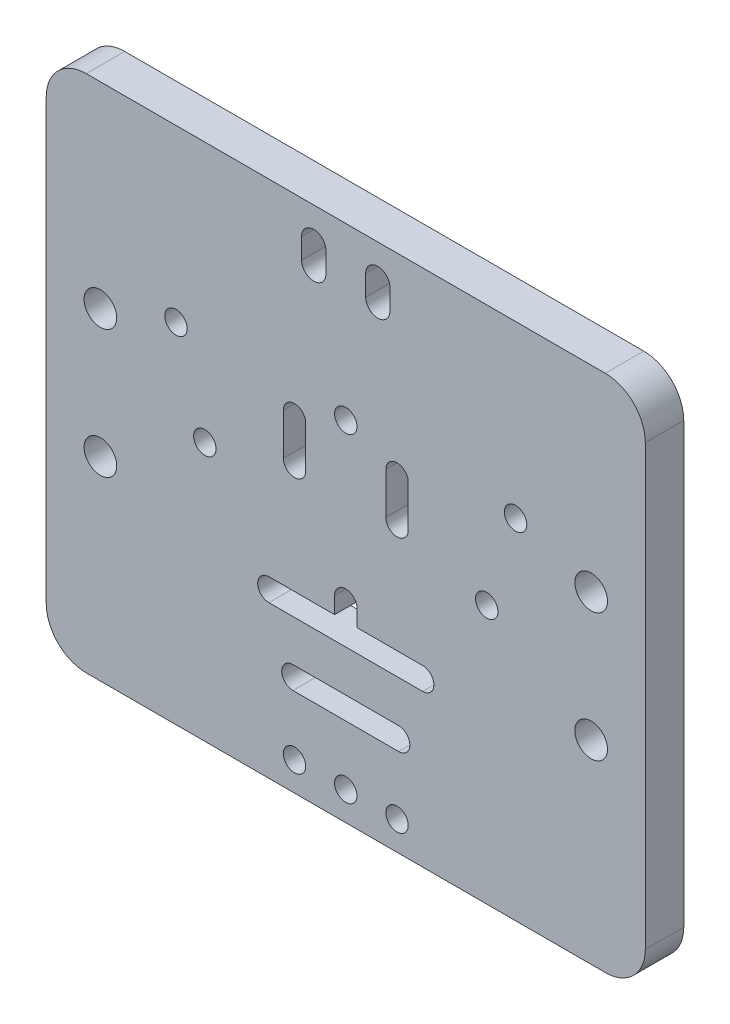
SolidWorks part; units mm, degrees
material "Acrylic (Medium-high impact)"
ref_plane "Спереди" through (0, 0, 0) normal (0, 0, 1) x (1, 0, 0)
ref_plane "Сверху" through (0, 0, 0) normal (0, 1, 0) x (1, 0, 0)
ref_plane "Справа" through (0, 0, 0) normal (1, 0, 0) x (0, 0, -1)
sketch "Model" plane through (0, 0, 0) normal (0, 0, 1) x (1, 0, 0)
  line L0 (0, 0) -> (0, 91.7343) construction
  line L1 (5, 79.6063) -> (5, 68.5159) construction
  line L2 (-2.3648, 54.4) -> (2.3481, 54.4) construction
  line L3 (8, 54.1038) -> (8, 41.41) construction
  line L4 (38.3, 55.3072) -> (38.3, 25.5369) construction
  line L6 (5.2056, 25.5) -> (38.932, 25.5) construction
  line L9 (8, 7.117) -> (8, 1.8707) construction
  line L13 (34.6862, 30.35) -> (41.936, 30.35) construction
  line L14 (34.5552, 50.35) -> (42.4898, 50.35) construction
  line L15 (26.5, 56.989) -> (26.5, 51.9054) construction
  line L16 (23.9154, 54.4) -> (29.241, 54.4) construction
  line L17 (22, 42.5983) -> (22, 38.5529) construction
  line L18 (19.8952, 40.4) -> (24.0146, 40.4) construction
  line L19 (-5, 79.6063) -> (-5, 68.5159) construction
  line L20 (-3.1, 75.8) -> (-3.1, 72.6)
  line L21 (-6.9, 72.6) -> (-6.9, 75.8)
  line L22 (-6.9, 75.8) -> (-6.9, 72.6)
  line L23 (-3.1, 72.6) -> (-3.1, 75.8)
  line L24 (-34.5552, 50.35) -> (-42.4898, 50.35) construction
  line L25 (-34.6862, 30.35) -> (-41.936, 30.35) construction
  line L26 (-38.3, 55.3072) -> (-38.3, 25.5369) construction
  line L27 (-8, 7.117) -> (-8, 1.8707) construction
  line L33 (-19.8952, 40.4) -> (-24.0146, 40.4) construction
  line L34 (-22, 42.5983) -> (-22, 38.5529) construction
  line L35 (-23.9154, 54.4) -> (-29.241, 54.4) construction
  line L36 (-26.5, 56.989) -> (-26.5, 51.9054) construction
  line L37 (-8, 54.1038) -> (-8, 41.41) construction
  line L38 (-9.75, 50.9) -> (-9.75, 44.4)
  line L39 (-6.25, 44.4) -> (-6.25, 50.9)
  line L40 (-6.25, 50.9) -> (-6.25, 44.4)
  line L41 (-9.75, 44.4) -> (-9.75, 50.9)
  line L42 (-8.25, 15.5) -> (8.25, 15.5) construction
  line L1661 (3.1, 72.6) -> (3.1, 75.8)
  line L1674 (6.9, 75.8) -> (6.9, 72.6)
  line L1730 (46.75, 74.75) -> (46.75, 6.25)
  line L1743 (40.5, 0) -> (-40.5, 0)
  line L1756 (-46.75, 6.25) -> (-46.75, 74.75)
  line L1769 (-40.5, 81) -> (40.5, 81)
  line L1807 (8.25, 17.25) -> (-8.25, 17.25)
  line L1820 (-8.25, 13.75) -> (8.25, 13.75)
  line L2052 (6.9, 72.6) -> (6.9, 75.8)
  line L2065 (3.1, 75.8) -> (3.1, 72.6)
  line L2109 (9.75, 44.4) -> (9.75, 50.9)
  line L2122 (6.25, 50.9) -> (6.25, 44.4)
  line L2254 (-1.75, 29.85) -> (-1.75, 27.25)
  line L2255 (-1.75, 27.25) -> (-12, 27.25)
  line L2268 (-12, 23.75) -> (12, 23.75)
  line L2281 (12, 27.25) -> (1.75, 27.25)
  line L2282 (1.75, 27.25) -> (1.75, 29.85)
  line L2413 (6.25, 44.4) -> (6.25, 50.9)
  line L2426 (9.75, 50.9) -> (9.75, 44.4)
  line L2519 (8.25, 13.75) -> (-8.25, 13.75)
  line L2532 (-8.25, 17.25) -> (8.25, 17.25)
  line L2808 (1.75, 29.85) -> (1.75, 27.25)
  line L2809 (1.75, 27.25) -> (12, 27.25)
  line L2822 (12, 23.75) -> (-12, 23.75)
  line L2835 (-12, 27.25) -> (-1.75, 27.25)
  line L2836 (-1.75, 27.25) -> (-1.75, 29.85)
  arc A0 (-46.75, 74.75) -> (-40.5, 81) centre (-40.5, 74.75) cw
  arc A1 (40.5, 81) -> (46.75, 74.75) centre (40.5, 74.75) cw
  arc A2 (46.75, 6.25) -> (40.5, 0) centre (40.5, 6.25) cw
  arc A3 (-46.75, 6.25) -> (-40.5, 0) centre (-40.5, 6.25) ccw
  arc A4 (6.9, 75.8) -> (3.1, 75.8) centre (5, 75.8) ccw
  arc A5 (3.1, 72.6) -> (6.9, 72.6) centre (5, 72.6) ccw
  circle A7 centre (0, 4.5) radius 1.75
  circle A8 centre (8, 4.5) radius 1.75
  arc A11 (-8.25, 17.25) -> (-8.25, 13.75) centre (-8.25, 15.5) ccw
  arc A12 (8.25, 13.75) -> (8.25, 17.25) centre (8.25, 15.5) ccw
  arc A13 (1.75, 29.85) -> (-1.75, 29.85) centre (0, 29.85) ccw
  arc A14 (12, 23.75) -> (12, 27.25) centre (12, 25.5) ccw
  arc A15 (-12, 23.75) -> (-12, 27.25) centre (-12, 25.5) cw
  circle A16 centre (38.3, 50.35) radius 2.55
  circle A17 centre (38.3, 30.35) radius 2.55
  arc A18 (-3.1, 72.6) -> (-6.9, 72.6) centre (-5, 72.6) cw
  arc A19 (-6.9, 75.8) -> (-3.1, 75.8) centre (-5, 75.8) cw
  circle A20 centre (-38.3, 30.35) radius 2.55
  circle A21 centre (-38.3, 50.35) radius 2.55
  circle A22 centre (-8, 4.5) radius 1.75
  circle A26 centre (0, 54.4) radius 1.75
  circle A27 centre (26.5, 54.4) radius 1.75
  circle A28 centre (22, 40.4) radius 1.75
  arc A29 (9.75, 50.9) -> (6.25, 50.9) centre (8, 50.9) ccw
  arc A30 (9.75, 44.4) -> (6.25, 44.4) centre (8, 44.4) cw
  circle A31 centre (-22, 40.4) radius 1.75
  circle A32 centre (-26.5, 54.4) radius 1.75
  arc A33 (-9.75, 44.4) -> (-6.25, 44.4) centre (-8, 44.4) ccw
  arc A34 (-9.75, 50.9) -> (-6.25, 50.9) centre (-8, 50.9) cw
  dimension "D1" = 6.25
  dimension "D7" = 1.9
  dimension "D9" = 15.5
  dimension "D15" = 3.5
  dimension "D17" = 3.5
  dimension "D41" = 5.1
  dimension "D43" = 3.5
  dimension "D44" = 3.5
  dimension "D2" = 81
  dimension "D3" = 81
  dimension "D4" = 5
  dimension "D5" = 3.2
  dimension "D6" = 3.8
  dimension "D8" = 5.2
  dimension "D10" = 16
  dimension "D11" = 25.5
  dimension "D12" = 4.5
  dimension "D13" = 8
  dimension "D22" = 3.5
  dimension "D23" = 2.6
  dimension "D24" = 3.5
  dimension "D25" = 3.5
  dimension "D26" = 16.5
  dimension "D29" = 24
  dimension "D33" = 8
  dimension "D34" = 22
  dimension "D35" = 26.5
  dimension "D36" = 38.3
  dimension "D37" = 20
  dimension "D38" = 30.35
  dimension "D39" = 26.6
  dimension "D40" = 40.6
  dimension "D46" = 6.5
  dimension "D48" = 3.5
extrude "Base" add sketch "Model" along normal blind 6 contours L1756 A3 L1743 A2 L1730 A1 L1769 A0 A31 A28 A27 A26 A22 A20 A17 A16 A12 L1820 A11 L1807 A8 A7 A5 L1661 A4 L1674 L2268 A15 L2255 L2254 region at (0, 40.7608, 0)
